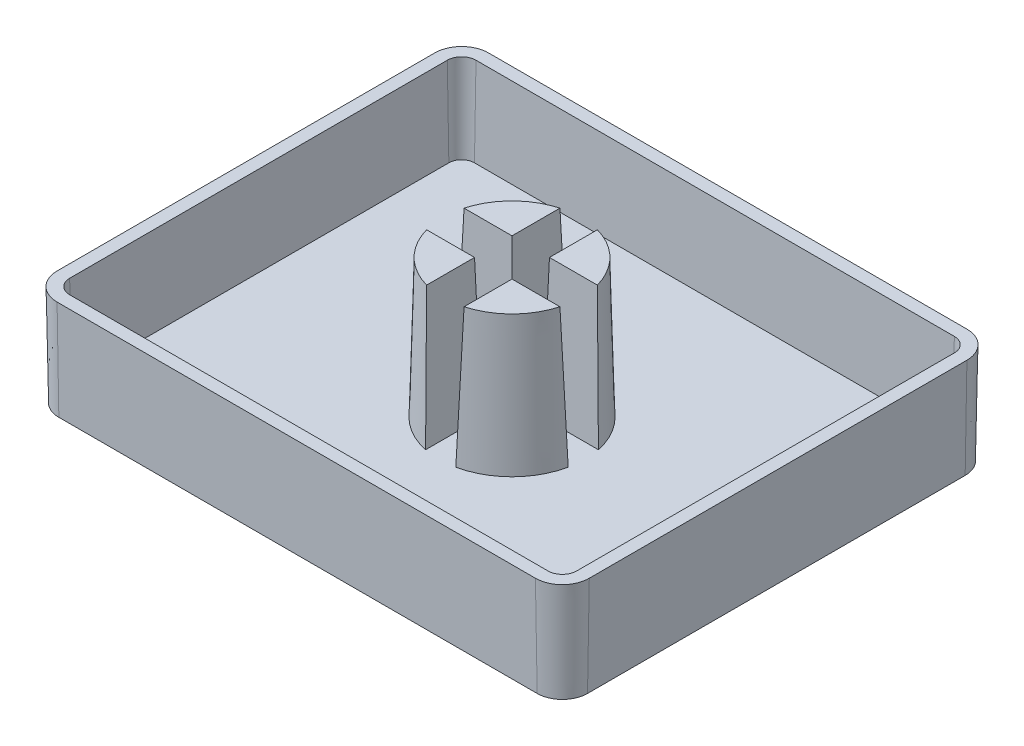
SolidWorks part; units mm, degrees
ref_plane "Front Plane" through (0, 0, 0) normal (0, 0, 1) x (1, 0, 0)
ref_plane "Top Plane" through (0, 0, 0) normal (0, 1, 0) x (1, 0, 0)
ref_plane "Right Plane" through (0, 0, 0) normal (1, 0, 0) x (0, 0, -1)
sketch "Sketch1" plane through (0, 0, 0) normal (0, 1, 0) x (1, 0, 0)
  line L1 (-9.5, -8.5) -> (9.5, -8.5)
  line L2 (-10.5, -7.5) -> (-10.5, 7.5)
  line L3 (-9.5, 8.5) -> (9.5, 8.5)
  line L4 (10.5, -7.5) -> (10.5, 7.5)
  line L5 (-10.5, -8.5) -> (10.5, 8.5) construction
  line L6 (-10.5, 8.5) -> (10.5, -8.5) construction
  arc A0 (-10.5, 7.5) -> (-9.5, 8.5) centre (-9.5, 7.5) cw
  arc A1 (10.5, 7.5) -> (9.5, 8.5) centre (9.5, 7.5) ccw
  arc A2 (10.5, -7.5) -> (9.5, -8.5) centre (9.5, -7.5) cw
  arc A3 (-9.5, -8.5) -> (-10.5, -7.5) centre (-9.5, -7.5) cw
  point P0 (0, 0)
  dimension "D3" = 1
  dimension "D1" = 21
  dimension "D2" = 17
extrude "Boss-Extrude1" add sketch "Sketch1" along normal blind 4 draft 1 draft outward yes
shell "Shell1" thickness 0.5 removed face at (0, 4, 0)
sketch "Sketch2" plane through (0, 0.5, 0) normal (0, 1, 0) x (1, 0, 0)
  line L0 (-0.6, 2.8319) -> (-0.6, 0.6)
  line L1 (-2.8319, 0.6) -> (-0.6, 0.6)
  line L2 (0, -2.2) -> (0, 2.2) construction
  line L3 (-2.2, 0) -> (2.2, 0) construction
  line L4 (-2.8319, -0.6) -> (-0.6, -0.6)
  line L5 (0.6, 2.8319) -> (0.6, 0.6)
  line L6 (0.6, 0.6) -> (2.8319, 0.6)
  line L7 (0.6, -0.6) -> (2.8319, -0.6)
  line L8 (0.6, -0.6) -> (0.6, -2.8319)
  line L9 (-0.6, -0.6) -> (-0.6, -2.8319)
  arc A0 (-0.6, 2.8319) -> (-2.8319, 0.6) centre (0, 0) ccw
  arc A1 (-2.8319, -0.6) -> (-0.6, -2.8319) centre (0, 0) ccw
  arc A2 (2.8319, 0.6) -> (0.6, 2.8319) centre (0, 0) ccw
  arc A3 (0.6, -2.8319) -> (2.8319, -0.6) centre (0, 0) ccw
  dimension "D1" = 0.6
  dimension "D2" = 0.6
extrude "Boss-Extrude2" add sketch "Sketch2" along normal blind 5.5 draft 1.5
